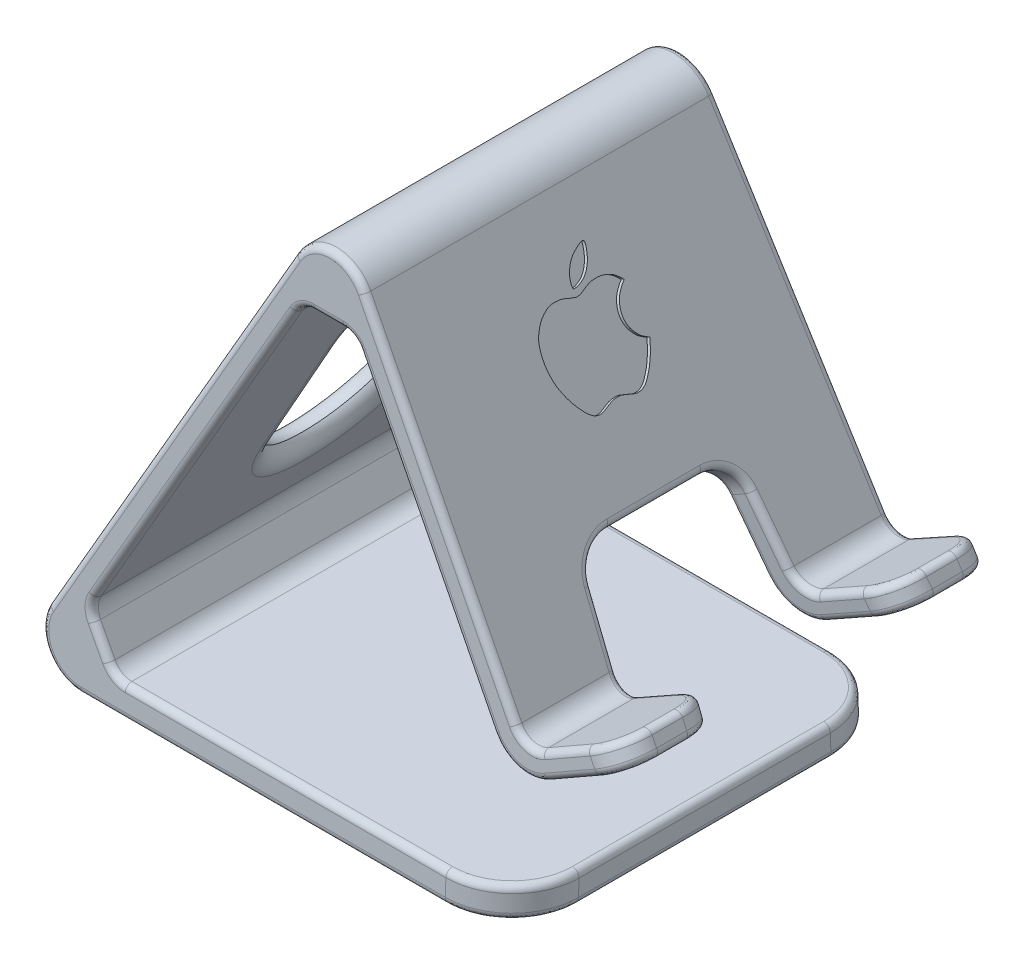
SolidWorks part; units mm, degrees
material "POM 乙缩醛共聚物"
ref_plane "前视基准面" through (0, 0, 0) normal (0, 0, 1) x (1, 0, 0)
ref_plane "上视基准面" through (0, 0, 0) normal (0, 1, 0) x (1, 0, 0)
ref_plane "右视基准面" through (0, 0, 0) normal (1, 0, 0) x (0, 0, -1)
sketch "草图1" plane through (0, 0, 0) normal (0, 0, 1) x (1, 0, 0)
  line L0 (0, 0) -> (-75, 0)
  line L1 (-75, 0) -> (-30, 80)
  line L2 (-30, 80) -> (1, 24.8889)
  line L3 (1, 24.8889) -> (14.5094, 32.4879)
  line L4 (14.5094, 32.4879) -> (16.2253, 29.4374)
  line L5 (16.2253, 29.4374) -> (-0.7704, 19.8773)
  line L6 (-0.7704, 19.8773) -> (-30, 71.8411)
  line L7 (-30, 71.8411) -> (-67.8794, 4.5)
  line L8 (-67.8794, 4.5) -> (0, 4.5)
  line L9 (0, 4.5) -> (0, 0)
  point P3 (0, 0)
  dimension "D1" = 75
  dimension "D2" = 4.5
  dimension "D3" = 4
  dimension "D4" = 80
  dimension "D5" = 45
  dimension "D6" = 4
  dimension "D7" = 3.5
  dimension "D8" = 15.5
  dimension "D10" = 31
extrude "凸台-拉伸1" add sketch "草图1" along normal mid plane 58
sketch "草图3" plane through (0, 0, 0) normal (1, 0, 0) x (0, 0, -1)
  line L0 (-29, 0) -> (-29, 80)
  line L1 (-29, 80) -> (-26, 80)
  line L2 (-29, 80) -> (29, 80) construction
  line L3 (-26, 80) -> (-29, 0)
  line L4 (0, 0) -> (0, 80) construction
  line L5 (26, 80) -> (29, 0)
  line L6 (29, 80) -> (26, 80)
  line L7 (29, 0) -> (29, 80)
  dimension "D1" = 52
extrude "切除-拉伸1" cut sketch "草图3" against normal through all both and the other way through all
sketch "草图4" plane through (11.3947, 6.4095, 0) normal (0.8716, 0.4903, 0) x (0, 0, -1)
  line L0 (0, 0) -> (0, 38) construction
  line L1 (11.5, 38) -> (-11.5, 38)
  line L2 (-11.5, 38) -> (-14, 13)
  line L3 (-14, 13) -> (14, 13)
  line L4 (11.5, 38) -> (14, 13)
  line L5 (-29, 0) -> (29, 0) construction
  point P7 (0, 13)
  dimension "D1" = 23
  dimension "D2" = 28
  dimension "D3" = 13
  dimension "D4" = 25
extrude "切除-拉伸2" cut sketch "草图4" against normal up to next and the other way through all
fillet "圆角1" radius 10 2 edges at (0, 2.25, -28.9156) (0, 2.25, 28.9156)
chamfer "倒角1" distance 8 distance2 8 2 edges at (-30, 71.8411, 0) (-67.8794, 4.5, 0)
fillet "圆角2" radius 6 2 edges at (-75, 0, 0) (-30, 80, 0)
fillet "圆角3" radius 3 2 edges at (1, 24.8889, -20.6232) (1, 24.8889, 20.6232)
fillet "圆角4" radius 6 2 edges at (-0.7704, 19.8773, -20.8922) (-0.7704, 19.8773, 20.8922)
fillet "圆角5" radius 5 4 edges at (15.3674, 30.9627, -27.8389) (15.3674, 30.9627, -13.3548) (15.3674, 30.9627, 13.3548) (15.3674, 30.9627, 27.8389)
sketch "草图5" plane through (0, 0, 0) normal (0, -1, 0) x (1, 0, 0)
  line L0 (0, 0) -> (-56, 0) construction
  circle A0 centre (-10, 18.993) radius 7.5
  circle A1 centre (-10, -18.993) radius 7.5
  circle A2 centre (-56, 0) radius 7.5
  ellipse E0 centre (-10, 18.993) end of major axis (-10, 8.9859) minor radius 10 (0, 18.993) -> (-10, 29) ccw construction
  ellipse E1 centre (-10, -18.993) end of major axis (-10, -8.9859) minor radius 10 (-10, -29) -> (0, -18.993) ccw construction
  dimension "D1" = 15
  dimension "D2" = 15
  dimension "D3" = 15
  dimension "D4" = 56
extrude "凸台-拉伸2" add sketch "草图5" along normal blind 1
sketch "草图6" plane through (-56.9733, 32.0475, 0) normal (-0.8716, 0.4903, 0) x (0, 0, 1)
  line L0 (0, -32.5105) -> (0, 50.3515) construction
  line L1 (-28.9711, -32.5105) -> (28.9711, -32.5105) construction
  line L2 (26.2628, 50.3515) -> (-26.2628, 50.3515) construction
  line L3 (0, -0.5105) -> (0, 19.4895) construction
  line L4 (-10, -0.5105) -> (-10, 19.4895)
  line L5 (10, -0.5105) -> (10, 19.4895)
  arc A0 (-10, -0.5105) -> (10, -0.5105) centre (0, -0.5105) ccw
  arc A1 (10, 19.4895) -> (-10, 19.4895) centre (0, 19.4895) ccw
  point P8 (0, 9.4895)
  dimension "D1" = 20
  dimension "D2" = 32
  dimension "D3" = 20
extrude "切除-拉伸3" cut sketch "草图6" against normal up to next
sketch "草图7" plane through (-56.9733, 32.0475, 0) normal (-0.8716, 0.4903, 0) x (0, 0, 1)
  text T0 "PHONE STAND" font "@Adobe 黑体 Std R" height 5
extrude "切除-拉伸4" cut sketch "草图7" against normal blind 0.3
fillet "圆角6" radius 5 2 edges at (-8.9784, 38.5488, 11.5) (-8.9784, 38.5488, -11.5)
sketch "草图9" plane through (11.3947, 6.4095, 0) normal (0.8716, 0.4903, 0) x (0, 0, -1)
  line L0 (90.6889, 361.4998) -> (517.3555, 361.4998) construction
  spline S0 degree 3 poles (3.0934, 65.5966) (3.5127, 67.2544) (1.9842, 66.5897) (0.9413, 65.9727) (0.0187, 64.9041) (-0.3876, 63.6853) (-0.3876, 63.0851) (-0.3385, 62.7889) (0.1018, 62.7989) (0.5357, 62.8635) (1.3575, 63.1959) (2.1108, 63.803) (2.7715, 64.7358) (3.0934, 65.5966) (3.5127, 67.2544) (1.9842, 66.5897) knots -0.283788 -0.190653 -0.090906 0 0.098748 0.193179 0.336715 0.439146 0.490957 0.495813 0.510402 0.564699 0.638505 0.716212 0.809347 0.909094 1 1.098748 1.193179 1.336715 only from (3.2038, 66.8579) to (3.2038, 66.8579)
  spline S1 degree 3 poles (0.1284, 61.8533) (-0.1549, 61.8802) (-0.3845, 61.8051) (-0.6698, 61.9898) (-1.0549, 62.0266) (-1.4292, 62.2431) (-1.8545, 62.338) (-2.2485, 62.4889) (-2.7197, 62.5468) (-3.1983, 62.5412) (-3.7261, 62.5713) (-4.2448, 62.446) (-4.7714, 62.2384) (-5.3283, 61.8941) (-5.9492, 61.4279) (-6.4914, 60.7319) (-7.0101, 59.9362) (-7.3373, 58.7433) (-7.4574, 57.2357) (-7.3176, 55.7356) (-6.9919, 54.4282) (-6.5697, 53.3192) (-5.9797, 52.1505) (-5.2729, 51.0945) (-4.5564, 50.2014) (-3.8723, 49.5914) (-3.2425, 49.3351) (-2.7191, 49.3189) (-2.2701, 49.4245) (-1.8151, 49.5779) (-1.376, 49.7695) (-0.9757, 49.9239) (-0.6429, 50.0091) (-0.2477, 50.0553) (0.1364, 50.0494) (0.5907, 50.0488) (0.984, 49.9067) (1.5264, 49.7152) (2.0274, 49.534) (2.4951, 49.3514) (2.912, 49.3492) (3.3598, 49.3703) (3.7954, 49.5665) (4.2245, 49.8307) (4.7484, 50.3734) (5.3049, 51.0212) (5.7371, 51.7309) (6.0787, 52.2872) (6.3432, 52.8125) (6.5862, 53.3366) (6.7197, 53.7328) (6.8127, 53.9279) (6.8406, 54.0185) (6.7741, 54.0414) (6.6941, 54.0853) (6.5313, 54.1608) (6.2447, 54.3412) (5.7956, 54.627) (5.2817, 55.2051) (4.782, 55.9232) (4.4393, 56.981) (4.4215, 58.0845) (4.7544, 59.111) (5.1807, 59.8829) (5.7072, 60.3688) (6.0452, 60.6973) (6.2441, 60.796) (6.3362, 60.8637) (6.3677, 60.8973) (6.3389, 60.9802) (6.1953, 61.1454) (6.0247, 61.3269) (5.7429, 61.6059) (5.2878, 61.9933) (4.5511, 62.3277) (3.797, 62.5836) (2.9755, 62.6307) (2.2418, 62.6117) (1.6097, 62.3954) (1.0428, 62.2407) (0.5439, 61.9663) (0.1284, 61.8533) (-0.1549, 61.8802) (-0.3845, 61.8051) knots -0.025842 -0.013461 -0.003385 0 0.004042 0.010764 0.0193 0.027766 0.036941 0.046117 0.053713 0.066073 0.075742 0.086172 0.098707 0.110591 0.126531 0.146362 0.164755 0.184805 0.22191 0.25777 0.27732 0.30501 0.330889 0.358049 0.383333 0.401597 0.413959 0.424488 0.433376 0.442334 0.454132 0.462965 0.468804 0.475309 0.487471 0.492554 0.503234 0.512897 0.528196 0.536258 0.543553 0.55372 0.563678 0.57262 0.584748 0.609985 0.625282 0.635985 0.650341 0.661455 0.672051 0.675079 0.676058 0.676833 0.678795 0.681878 0.687617 0.699825 0.715072 0.734766 0.75355 0.78298 0.801083 0.819837 0.836696 0.844939 0.849133 0.850454 0.851192 0.852838 0.856152 0.864635 0.87413 0.883786 0.899902 0.916603 0.933058 0.950396 0.961456 0.974158 0.986539 0.996615 1 1.004042 1.010764 1.0193 only from (-0.1443, 61.8686) to (-0.1443, 61.8686)
extrude "切除-拉伸5" cut sketch "草图9" against normal blind 0.5
fillet "圆角7" radius 3 4 edges at (-59.8794, 4.5, 0) (-63.9573, 11.4726, 0) (-26.0779, 64.8685, 0) (-33.9221, 64.8685, 0)
fillet "圆角9" radius 2 4 edges at (-42.5157, 57.7498, 0) (-52.321, 40.3183, 10) (-62.1262, 22.8868, 0) (-52.321, 40.3183, -10)
fillet "圆角10" radius 3 4 edges at (-58.6399, 20.9257, 0) (-48.8347, 38.3572, 10) (-39.0294, 55.7888, 0) (-48.8347, 38.3572, -10)
fillet "圆角11" radius 1 32 edges at (6.9232, 28.2207, 27.9417) (1.3351, 26.0855, 28.0218) (-12.6207, 49.1034, 27.1586) (-30, 73.7616, 26.2339) (-52.5999, 39.8224, 27.5067) (-69.9202, 2.9709, 28.8886) (-37.3705, 0, 29) (-2.9289, 0, 26.069) (0, 0, 0) (-2.9289, 0, -26.069) (-37.3705, 0, -29) (-69.9202, 2.9709, -28.8886) (-52.5999, 39.8224, -27.5067) (-30, 73.7616, -26.2339) (-12.6207, 49.1034, -27.1586) (1.3351, 26.0855, -28.0218) (6.9232, 28.2207, -27.9417) (13.2612, 31.7858, -26.3749) (14.5094, 32.4879, -20.5374) (13.233, 31.77, -14.6515) (6.8831, 28.1982, -13.1798) (1.3351, 26.0855, -13.0919) (-2.7493, 31.5544, -12.415) (-6.6015, 38.4026, -10.3301) (-7.2353, 39.5294, 0) (-6.6015, 38.4026, 10.3301) (-2.7493, 31.5544, 12.415) (1.3351, 26.0855, 13.0919) (6.8831, 28.1982, 13.1798) (13.233, 31.77, 14.6515) (14.5094, 32.4879, 20.5374) (13.2612, 31.7858, 26.3749)
fillet "圆角12" radius 1 40 edges at (16.2253, 29.4374, 20.7696) (14.9489, 28.7195, 15.0015) (8.1633, 24.9025, 13.5298) (-0.1003, 22.2706, 13.354) (-6.1131, 29.3754, 12.44) (-10.0878, 36.4416, 10.3301) (-10.7216, 37.5683, 0) (-10.0878, 36.4416, -10.3301) (-6.1131, 29.3754, -12.44) (-0.1003, 22.2706, -13.354) (8.1633, 24.9025, -13.5298) (14.9489, 28.7195, -15.0015) (16.2253, 29.4374, -20.7696) (14.9771, 28.7353, -26.4893) (8.2033, 24.925, -28.0653) (-0.1003, 22.2706, -28.1649) (-14.4648, 44.223, -27.3416) (-26.3179, 64.4581, -26.5828) (-30, 64.8685, -26.5674) (-33.6821, 64.4581, -26.5828) (-48.9479, 38.1559, -27.5692) (-63.4988, 11.4765, -28.5696) (-61.9183, 7.9863, -28.7005) (-59.6512, 4.8977, -28.8163) (-34.0793, 4.5, -28.8313) (-2.9289, 4.5, -25.9003) (0, 4.5, 0) (-2.9289, 4.5, 25.9003) (-34.0793, 4.5, 28.8313) (-59.6512, 4.8977, 28.8163) (-61.9183, 7.9863, 28.7005) (-63.4988, 11.4765, 28.5696) (-48.9479, 38.1559, 27.5692) (-33.6821, 64.4581, 26.5828) (-30, 64.8685, 26.5674) (-26.3179, 64.4581, 26.5828) (-14.4648, 44.223, 27.3416) (-0.1003, 22.2706, 28.1649) (8.2033, 24.925, 28.0653) (14.9771, 28.7353, 26.4893)
